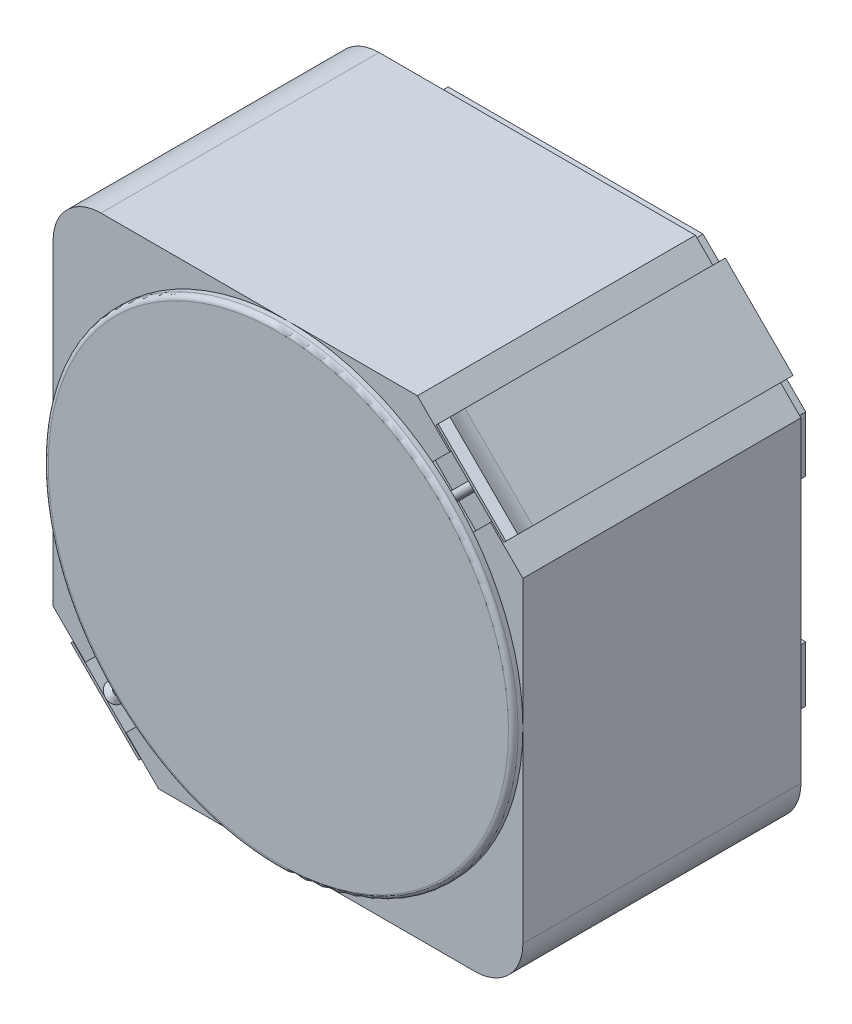
SolidWorks part; units mm, degrees
ref_plane "Спереди" through (0, 0, 0) normal (0, 0, 1) x (1, 0, 0)
ref_plane "Сверху" through (0, 0, 0) normal (0, 1, 0) x (1, 0, 0)
ref_plane "Справа" through (0, 0, 0) normal (1, 0, 0) x (0, 0, -1)
sketch "Эскиз1" plane through (0, 0, 0) normal (0, 0, 1) x (1, 0, 0)
  line L0 (-2.45, -1.35) -> (-1.35, -2.45)
  line L1 (-1.95, 2.45) -> (1.35, 2.45)
  line L2 (-2.45, 1.95) -> (-2.45, -1.35)
  line L3 (-1.35, -2.45) -> (1.95, -2.45)
  line L4 (2.45, 1.35) -> (2.45, -1.95)
  line L5 (-2.45, 2.45) -> (2.45, -2.45) construction
  line L6 (-2.45, -2.45) -> (2.45, 2.45) construction
  line L7 (1.35, 2.45) -> (2.45, 1.35)
  arc A0 (-1.95, 2.45) -> (-2.45, 1.95) centre (-1.95, 1.95) ccw
  arc A1 (1.95, -2.45) -> (2.45, -1.95) centre (1.95, -1.95) ccw
  point P0 (0, 0)
  dimension "D1" = 0.5
  dimension "D2" = 4.9
extrude "Корпус" add sketch "Эскиз1" along normal blind 2.9 from offset 0.1
sketch "Эскиз2" plane through (0, 0, 3) normal (0, 0, 1) x (1, 0, 0)
  line L0 (-2.45, 1.95) -> (-2.45, -1.35) construction
  circle A0 centre (0, 0) radius 2.45
extrude "Сердечник" add sketch "Эскиз2" along normal blind 0.1 and the other way blind 1
fillet "Скругление1" radius 0.05 1 edges at (2.45, 0, 3.1)
ref_plane "Плоскость1" through (0.55, -0.55, 0) normal (0.7071, -0.7071, 0) x (0, 0, 1)
sketch "Эскиз6" plane through (0.55, -0.55, 0) normal (0.7071, -0.7071, 0) x (0, 0, 1)
  line L0 (2.908, -2.782) -> (2.995, -2.73)
  line L1 (2.995, -2.7) -> (0.125, -2.7)
  line L2 (2.715, -2.73) -> (0, -2.73)
  line L3 (0, -2.73) -> (0, -2.2)
  line L4 (0.125, -2.7) -> (0.125, -2.2)
  line L5 (0.125, -2.2) -> (0, -2.2)
  line L6 (2.995, -2.73) -> (2.995, -2.7)
  line L8 (0.1, -2.687) -> (3, -2.687) construction
  line L9 (3, -2.45) -> (3, -1.7324) construction
  line L11 (0.1, 0.3536) -> (0.1, 2.687) construction
  line L12 (3, -2.687) -> (0.1, -2.687) construction
  spline S0 degree 2 poles (2.715, -2.73) (2.8188, -2.7338) (2.908, -2.782) knots 0 0 0 1 1 1
  dimension "D2" = 0.5
  dimension "D3" = 0.013
  dimension "D4" = 0.025
  dimension "D5" = 0.005
  dimension "D6" = 0.082
  dimension "D7" = 0.087
  dimension "D8" = 120.867
  dimension "D9" = 0.28
  dimension "D10" = 0.1354
  dimension "D11" = 0.0295
  dimension "D12" = 0.03
extrude "вывод, бок" add sketch "Эскиз6" against normal blind 1 from offset 0.3 offset against normal yes
ref_point "Точка1"
ref_axis "Ось1" through (0, 0, 3.1) along (0, 0, -1)
sketch "Эскиз8" plane through (0, 0, 3) normal (0, 0, 1) x (1, 0, 0)
  line L0 (2.1121, 1.6879) -> (1.6879, 2.1121)
  line L2 (1.6879, 2.1121) -> (1.3357, 1.76)
  line L3 (-1.6879, -2.1121) -> (-1.3357, -1.76)
  line L4 (1.5479, 1.5479) -> (0, 0) construction
  line L5 (2.1121, 1.6879) -> (1.76, 1.3357)
  line L6 (1.76, 1.3357) -> (1.3357, 1.76)
  line L7 (-1.76, -1.3357) -> (-1.3357, -1.76)
  line L8 (-2.1121, -1.6879) -> (-1.76, -1.3357)
  line L9 (-2.1121, -1.6879) -> (-1.6879, -2.1121)
  line L10 (2.45, 1.35) -> (1.35, 2.45) construction
  dimension "D2" = 0.498
  dimension "D4" = 0.6
  dimension "D1" = 2
extrude "Вытянуть8" cut sketch "Эскиз8" against normal blind 0.2
sketch "Эскиз9" plane through (1.9092, 1.9092, 0) normal (-0.7071, -0.7071, 0) x (0, 0, 1)
  line L1 (0, 0) -> (2.899, 0) construction
  line L2 (2.995, 0.5222) -> (2.995, -0.4778) construction
  circle A0 centre (2.899, 0) radius 0.046
  dimension "D1" = 0.092
  dimension "D2" = 0.096
extrude "Бобышка-Вытянуть1" add sketch "Эскиз9" along normal up to next (0.511 mm away) and the other way blind 0.05 draft 45 from offset 0.05 other way draft outward yes
pattern_circular "Круговой массив3" count 2 over 360 about axis through (0, 0, 3.1) along (0, 0, -1) of "вывод, бок", "Бобышка-Вытянуть1"
sketch "Эскиз13" plane through (0, 0, 0.1) normal (0, 0, -1) x (-1, 0, 0)
  line L1 (-2.45, -1.95) -> (-2.45, 1.35) construction
  line L2 (0, -2.4) -> (0, 0) construction
  line L3 (2.45, 1.95) -> (2.45, -1.35) construction
  line L4 (1.5308, -2.2692) -> (1.35, -2.45) construction
  line L5 (55, 0) -> (-55, 0) construction
  line L6 (1.8, 0.7488) -> (2.4, 0.7488)
  line L7 (1.35, -2.45) -> (-1.95, -2.45) construction
  line L8 (2.4, 0.7488) -> (2.4, 1.3288)
  line L9 (1.3288, 2.4) -> (2.4, 1.3288)
  line L10 (-1.3288, 2.4) -> (1.3288, 2.4)
  line L11 (-2.4, 1.3288) -> (-1.3288, 2.4)
  line L12 (-2.4, -0.7488) -> (-1.8, -0.7488)
  line L13 (-2.4, -1.3288) -> (-2.4, -0.7488)
  line L16 (-2.4, -1.3288) -> (-1.3288, -2.4)
  line L17 (-2.4, 1.3288) -> (-2.4, 0.7488)
  line L18 (-1.3288, -2.4) -> (1.3288, -2.4)
  line L19 (1.3288, -2.4) -> (2.4, -1.3288)
  line L20 (2.4, -0.7488) -> (2.4, -1.3288)
  line L21 (1.8, -0.7488) -> (2.4, -0.7488)
  line L22 (-2.4, 0.7488) -> (-1.8, 0.7488)
  arc A0 (-1.8, -0.7488) -> (1.8, -0.7488) centre (0, 0) ccw
  arc A1 (-1.8, 0.7488) -> (1.8, 0.7488) centre (0, 0) cw
  circle A2 centre (0, 0) radius 2.45 construction
  dimension "D2" = 0.5004
  dimension "D3" = 0.6
  dimension "D5" = 0.05
  dimension "D6" = 0.0503
  dimension "D7" = 0.05
  dimension "D1" = 0.58
extrude "Выводы низ" add sketch "Эскиз13" along normal up to surface (0.1 mm away) up to face at (-1.7273, -1.7587, 0)
